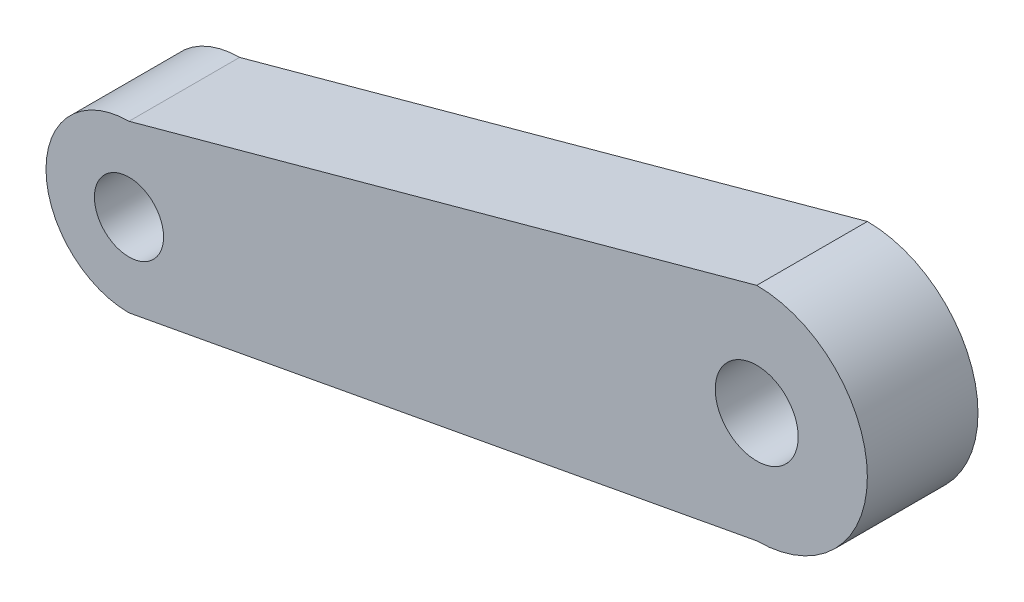
SolidWorks part; units mm, degrees
ref_plane "Спереди" through (0, 0, 0) normal (0, 0, 1) x (1, 0, 0)
ref_plane "Сверху" through (0, 0, 0) normal (0, 1, 0) x (1, 0, 0)
ref_plane "Справа" through (0, 0, 0) normal (1, 0, 0) x (0, 0, -1)
sketch "Эскиз1" plane through (0, 0, 0) normal (0, 0, 1) x (1, 0, 0)
  line L1 (-33.2939, -2.68) -> (12.0971, 9.7398)
  line L2 (-33.2939, -14.68) -> (12.0971, -6.2602)
  arc A0 (12.0971, -6.2602) -> (12.0971, 9.7398) centre (12.0971, 1.7398) ccw
  arc A1 (-33.2939, -2.68) -> (-33.2939, -14.68) centre (-33.2939, -8.68) ccw
  circle A2 centre (12.0971, 1.7398) radius 3
  circle A3 centre (-33.2939, -8.68) radius 2.5
extrude "Вытянуть1" add sketch "Эскиз1" along normal blind 8
